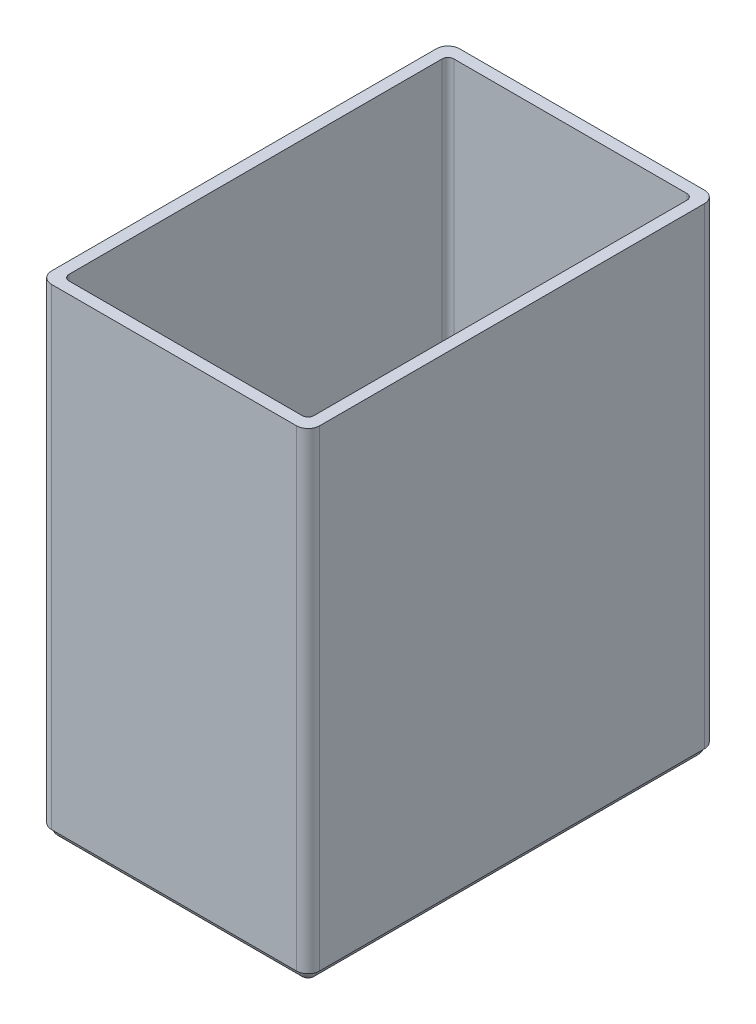
SolidWorks part; units mm, degrees
material "ABS"
ref_plane "Front Plane" through (0, 0, 0) normal (0, 0, 1) x (1, 0, 0)
ref_plane "Top Plane" through (0, 0, 0) normal (0, 1, 0) x (1, 0, 0)
ref_plane "Right Plane" through (0, 0, 0) normal (1, 0, 0) x (0, 0, -1)
sketch "Sketch1" plane through (0, 0, 0) normal (0, 1, 0) x (1, 0, 0)
  line L1 (-23, 35) -> (23, 35)
  line L2 (-23, 35) -> (-23, -35)
  line L3 (-23, -35) -> (23, -35)
  line L4 (23, 35) -> (23, -35)
  line L5 (-23, 35) -> (23, -35) construction
  line L6 (-23, -35) -> (23, 35) construction
  point P0 (0, 0)
  dimension "D1" = 46
  dimension "D2" = 70
extrude "Boss-Extrude1" add sketch "Sketch1" along normal mid plane 83
fillet "Fillet6" radius 2 4 edges at (-23, 0, -35) (23, 0, -35) (23, 0, 35) (-23, 0, 35)
shell "Shell1" thickness 2 removed face at (0, 41.5, 0)
fillet "Fillet8" radius 1 8 edges at (0, -39.5, -33) (21, -39.5, 0) (0, -39.5, 33) (-21, -39.5, 0) (21, 1, 33) (21, 1, -33) (-21, 1, -33) (-21, 1, 33)
sketch "Sketch3" plane through (0, -41.5, 0) normal (0, -1, 0) x (1, 0, 0)
  line L0 (-22.5, 33) -> (-22.5, -33)
  line L4 (-21, -34.5) -> (21, -34.5)
  line L5 (22.5, -33) -> (22.5, 33)
  line L6 (21, 34.5) -> (-21, 34.5)
  line L7 (-23, 33) -> (-23, -33)
  line L13 (-21, -35) -> (21, -35)
  line L14 (23, -33) -> (23, 33)
  line L15 (21, 35) -> (-21, 35)
  line L16 (-23, 33) -> (-23, -33)
  line L17 (-21, -35) -> (21, -35)
  line L18 (23, -33) -> (23, 33)
  line L19 (21, 35) -> (-21, 35)
  arc A0 (-22.5, -33) -> (-21, -34.5) centre (-21, -33) ccw
  arc A1 (21, -34.5) -> (22.5, -33) centre (21, -33) ccw
  arc A2 (22.5, 33) -> (21, 34.5) centre (21, 33) ccw
  arc A3 (-21, 34.5) -> (-22.5, 33) centre (-21, 33) ccw
  arc A4 (-23, -33) -> (-21, -35) centre (-21, -33) ccw
  arc A6 (21, -35) -> (23, -33) centre (21, -33) ccw
  arc A8 (23, 33) -> (21, 35) centre (21, 33) ccw
  arc A10 (-21, 35) -> (-23, 33) centre (-21, 33) ccw
  arc A12 (-23, -33) -> (-21, -35) centre (-21, -33) ccw
  arc A13 (21, -35) -> (23, -33) centre (21, -33) ccw
  arc A14 (23, 33) -> (21, 35) centre (21, 33) ccw
  arc A15 (-21, 35) -> (-23, 33) centre (-21, 33) ccw
  dimension "D2" = 0.5
  dimension "D1" = 0
extrude "Cut-Extrude1" cut sketch "Sketch3" against normal blind 2
fillet "Fillet9" radius 2 8 edges at (0, -41.5, 34.5) (22.0607, -41.5, 34.0607) (22.5, -41.5, 0) (22.0607, -41.5, -34.0607) (0, -41.5, -34.5) (-22.0607, -41.5, -34.0607) (-22.5, -41.5, 0) (-22.0607, -41.5, 34.0607)
